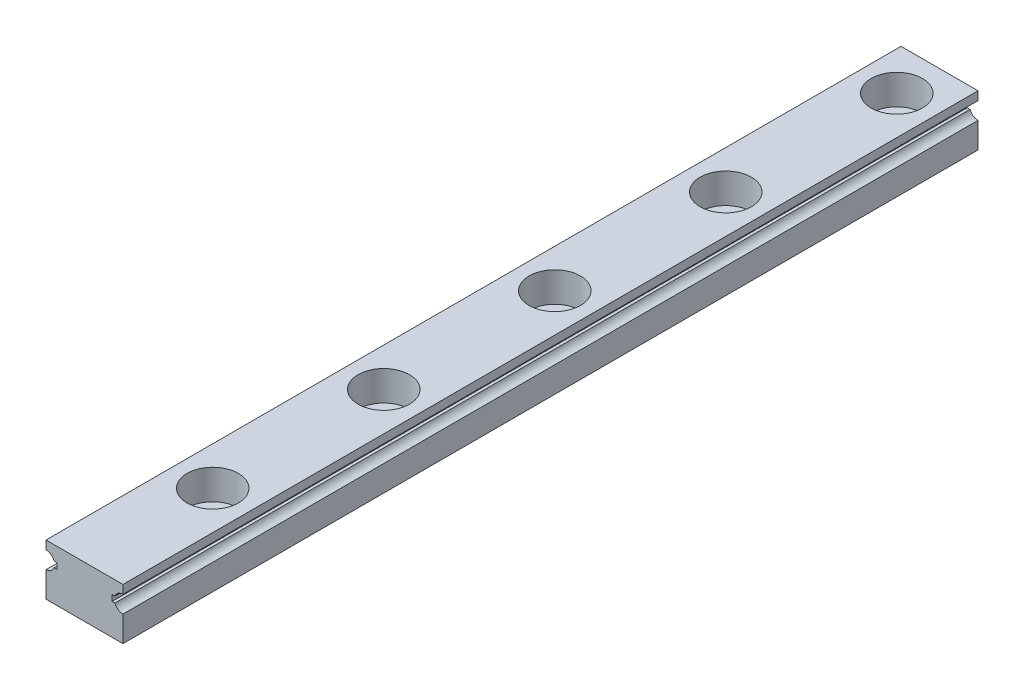
SolidWorks part; units mm, degrees
ref_plane "Front Plane" through (0, 0, 0) normal (0, 0, 1) x (1, 0, 0)
ref_plane "Top Plane" through (0, 0, 0) normal (0, 1, 0) x (1, 0, 0)
ref_plane "Right Plane" through (0, 0, 0) normal (1, 0, 0) x (0, 0, -1)
sketch "Sketch1" plane through (0, 0, 0) normal (0, 0, 1) x (1, 0, 0)
  line L0 (0, 0) -> (0, 5.7299) construction
  line L1 (-4.5, -3) -> (4.5, -3)
  line L2 (-4.5, -3) -> (-4.5, 0)
  line L3 (-4.5, 3) -> (4.5, 3)
  line L4 (4.5, -3) -> (4.5, 0)
  line L5 (-4.5, -3) -> (4.5, 3) construction
  line L6 (-4.5, 3) -> (4.5, -3) construction
  line L7 (-4.5, 2) -> (-4.5, 3)
  line L8 (-3.564, 0.648) -> (-3.2351, 0.648)
  line L9 (3.564, 0.648) -> (3.2351, 0.648)
  line L10 (-3.564, 1.352) -> (-3.2351, 1.352)
  line L11 (-3.2351, 0.648) -> (-3.2351, 1.352)
  line L12 (3.2351, 0.648) -> (3.2351, 1.352)
  line L13 (3.564, 1.352) -> (3.2351, 1.352)
  line L14 (4.5, 2) -> (4.5, 3)
  arc A0 (-3.564, 1.352) -> (-4.5, 2) centre (-4.5, 1) ccw
  arc A1 (-4.5, 0) -> (-3.564, 0.648) centre (-4.5, 1) ccw
  arc A2 (4.5, 0) -> (3.564, 0.648) centre (4.5, 1) cw
  arc A3 (3.564, 1.352) -> (4.5, 2) centre (4.5, 1) cw
  point P0 (0, 0)
  dimension "D3" = 1
  dimension "D1" = 9
  dimension "D2" = 6
  dimension "D4" = 2
extrude "Extrude1" add sketch "Sketch1" along normal blind 100
sketch "Sketch2" plane through (0, 3, 0) normal (0, 1, 0) x (1, 0, 0)
  line L0 (4.5, 0) -> (-4.5, 0) construction
  circle A0 centre (0, -5) radius 1.75
  circle A1 centre (0, -5) radius 3
  dimension "D1" = 3.5
  dimension "D2" = 6
  dimension "D3" = 5
extrude "Extrude2" cut sketch "Sketch2" against normal blind 3.5 contours A1
extrude "Extrude3" cut sketch "Sketch" against normal through all contours A0
sketch "Sketch" plane through (0, 3, 0) normal (0, 1, 0) x (1, 0, 0) same geometry as "Sketch2"
pattern_linear "LPattern1" count 30 spacing 20 along (0, 0, 1) of "Extrude2", "Extrude3"
